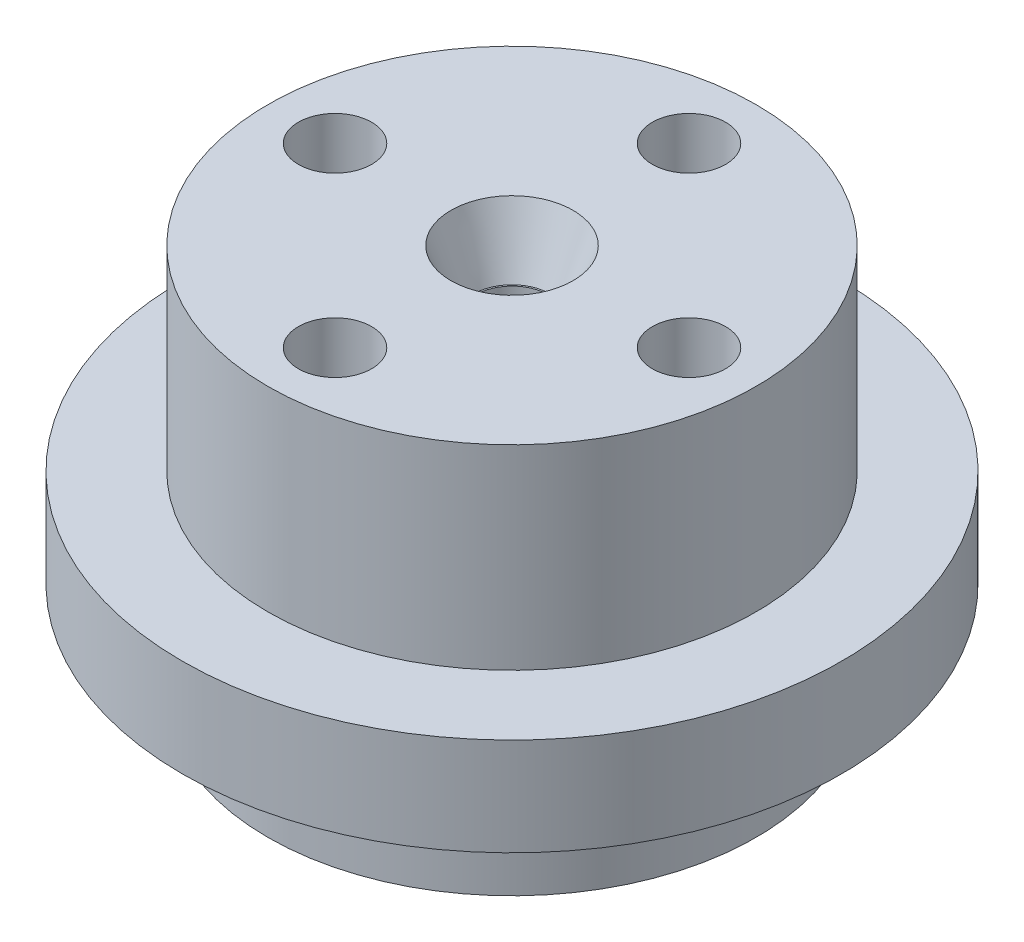
SolidWorks part; units mm, degrees
ref_plane "Front Plane" through (0, 0, 0) normal (0, 0, 1) x (1, 0, 0)
ref_plane "Top Plane" through (0, 0, 0) normal (0, 1, 0) x (1, 0, 0)
ref_plane "Right Plane" through (0, 0, 0) normal (1, 0, 0) x (0, 0, -1)
sketch "Sketch1" plane through (0, 0, 0) normal (0, 1, 0) x (1, 0, 0)
  circle A0 centre (0, 0) radius 10
extrude "Boss-Extrude1" add sketch "Sketch1" along normal blind 16
sketch "Sketch2" plane through (0, 16, 0) normal (0, 1, 0) x (1, 0, 0)
  circle A0 centre (0, 0) radius 1.5
extrude "Cut-Extrude1" cut sketch "Sketch2" against normal through all
sketch "Sketch3" plane through (0, 16, 0) normal (0, 1, 0) x (1, 0, 0)
  circle A0 centre (0, 0) radius 2.5
extrude "Cut-Extrude2" cut sketch "Sketch3" against normal blind 2.5 draft 20.5
ref_plane "Plane1" through (0, 6, 0) normal (0, -1, 0) x (-1, 0, 0)
sketch "Sketch5" plane through (0, 6, 0) normal (0, -1, 0) x (-1, 0, 0)
  circle A0 centre (0, 0) radius 13.5
extrude "Boss-Extrude2" add sketch "Sketch5" along normal blind 2 and the other way blind 2
sketch "Sketch7" plane through (0, 16, 0) normal (0, 1, 0) x (1, 0, 0)
  circle A0 centre (0, 7.25) radius 1.5
  circle A1 centre (7.25, 0) radius 1.5
  circle A2 centre (0, -7.25) radius 1.5
  circle A3 centre (-7.25, 0) radius 1.5
  point P12 (0, 0)
  dimension "D2" = 4
extrude "Cut-Extrude3" cut sketch "Sketch7" against normal blind 10
cosmetic thread "Cosmetic Thread1" parameters "D2"=4
cosmetic thread "Cosmetic Thread2" parameters "D2"=4
cosmetic thread "Cosmetic Thread3" parameters "D2"=4
cosmetic thread "Cosmetic Thread4" parameters "D2"=4
sketch "Sketch8" plane through (0, 6, 0) normal (0, 1, 0) x (1, 0, 0)
  circle A0 centre (-7.25, 0) radius 1
  circle A1 centre (0, 7.25) radius 1
  circle A2 centre (7.25, 0) radius 1
  circle A3 centre (0, -7.25) radius 1
  point P12 (0, 0)
  dimension "D1" = 4
extrude "Cut-Extrude4" cut sketch "Sketch8" against normal through all
cosmetic thread "Cosmetic Thread5" parameters "D2"=2.5
cosmetic thread "Cosmetic Thread6" parameters "D2"=2.5
cosmetic thread "Cosmetic Thread7" parameters "D2"=2.5
cosmetic thread "Cosmetic Thread8" parameters "D2"=2.5
sketch "Sketch9" plane through (0, 16, 0) normal (0, 1, 0) x (1, 0, 0)
  circle A0 centre (0, 0) radius 1.5
extrude "Cut-Extrude5" cut sketch "Sketch9" against normal through all
